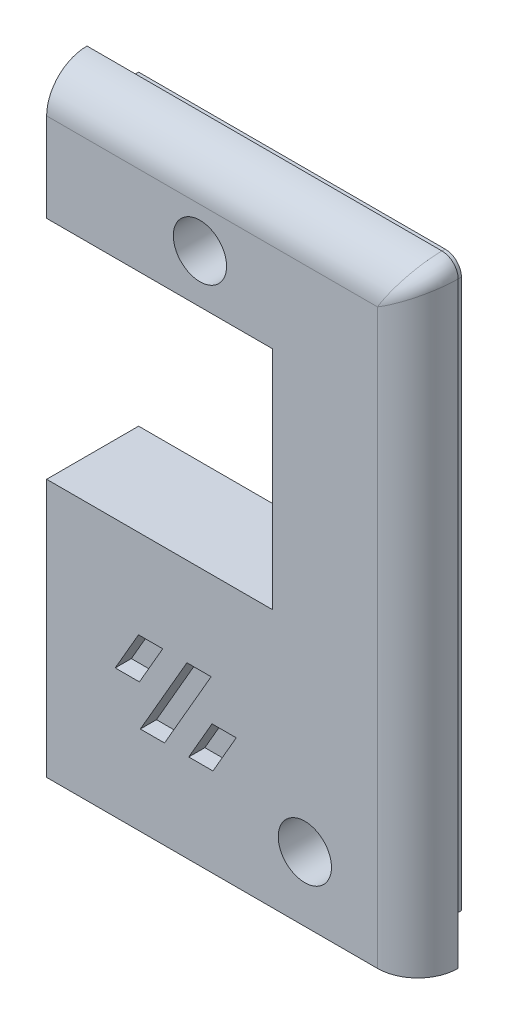
SolidWorks part; units mm, degrees
ref_plane "Front Plane" through (0, 0, 0) normal (0, 0, 1) x (1, 0, 0)
ref_plane "Top Plane" through (0, 0, 0) normal (0, 1, 0) x (1, 0, 0)
ref_plane "Right Plane" through (0, 0, 0) normal (1, 0, 0) x (0, 0, -1)
sketch "Sketch1" plane through (0, 0, 0) normal (0, 0, 1) x (1, 0, 0)
  line L1 (-14.899, 13.3838) -> (5.101, 13.3838)
  line L2 (-14.899, 13.3838) -> (-14.899, -21.6162)
  line L3 (-14.899, -21.6162) -> (5.101, -21.6162)
  line L4 (5.101, 13.3838) -> (5.101, -21.6162)
  dimension "D1" = 20
  dimension "D2" = 35
extrude "Boss-Extrude1" add sketch "Sketch1" along normal blind 3.2
fillet "Fillet1" radius 1 1 edges at (5.101, 13.3838, 1.6)
sketch "Sketch2" plane through (0, 0, 3.2) normal (0, 0, 1) x (1, 0, 0)
  line L0 (-14.899, 13.3838) -> (-14.899, -21.6162) construction
  line L1 (-14.899, -5.6162) -> (-0.899, -5.6162)
  line L2 (-14.899, -5.6162) -> (-14.899, 8.3838)
  line L3 (-14.899, 8.3838) -> (-0.899, 8.3838)
  line L4 (-0.899, -5.6162) -> (-0.899, 8.3838)
  line L5 (-14.899, -21.6162) -> (5.101, -21.6162) construction
  dimension "D1" = 16
  dimension "D2" = 14
  dimension "D3" = 14
extrude "Cut-Extrude1" cut sketch "Sketch2" against normal through all and the other way blind 12.5
sketch "Sketch4" plane through (0, 0, 3.2) normal (0, 0, 1) x (1, 0, 0)
  line L0 (4.101, 13.3838) -> (-14.899, 13.3838) construction
  line L1 (-14.899, 16.3838) -> (8.101, 16.3838)
  line L2 (-14.899, 16.3838) -> (-14.899, -21.6162)
  line L3 (-14.899, -21.6162) -> (8.101, -21.6162)
  line L4 (8.101, 16.3838) -> (8.101, -21.6162)
  line L5 (5.101, -21.6162) -> (5.101, 12.3838) construction
  dimension "D1" = 3
  dimension "D2" = 3
  dimension "D3" = 38
extrude "Boss-Extrude2" add sketch "Sketch4" along normal blind 2.5
fillet "Fillet2" radius 1 1 edges at (8.101, 16.3838, 4.45)
sketch "Sketch5" plane through (0, 0, 3.2) normal (0, 0, -1) x (-1, 0, 0)
  line L1 (0.899, 8.3838) -> (14.899, 8.3838)
  line L2 (0.899, 8.3838) -> (0.899, -5.6162)
  line L3 (0.899, -5.6162) -> (14.899, -5.6162)
  line L4 (14.899, 8.3838) -> (14.899, -5.6162)
extrude "Cut-Extrude2" cut sketch "Sketch5" against normal blind 2.5
fillet "Fillet3" radius 2.5 3 edges at (8.101, -3.1162, 5.7) (7.8081, 16.0909, 5.7) (-3.899, 16.3838, 5.7)
sketch "Sketch6" plane through (0, 0, 0) normal (0, 0, -1) x (-1, 0, 0)
  line L0 (14.899, -21.6162) -> (-5.101, -21.6162) construction
  line L1 (0.899, -5.6162) -> (0.899, 8.3838) construction
  circle A0 centre (-2.101, 5.3838) radius 1.4
  dimension "D1" = 2.8
  dimension "D2" = 27
  dimension "D3" = 3
sketch "Sketch12" plane through (0, 0, 5.7) normal (0, 0, 1) x (1, 0, 0)
  line L0 (-9.2056, -11.1162) -> (-7.7056, -11.1162)
  line L1 (-7.7056, -11.1162) -> (-9.149, -13.6162)
  line L2 (-9.149, -13.6162) -> (-10.649, -13.6162)
  line L3 (-10.649, -13.6162) -> (-9.2056, -11.1162)
  line L4 (-6.2056, -11.1162) -> (-4.7056, -11.1162)
  line L5 (-4.7056, -11.1162) -> (-7.5924, -16.1162)
  line L6 (-7.5924, -16.1162) -> (-9.0924, -16.1162)
  line L7 (-9.0924, -16.1162) -> (-6.2056, -11.1162)
  line L8 (-6.0924, -16.1162) -> (-4.5924, -16.1162)
  line L9 (-4.5924, -16.1162) -> (-3.149, -13.6162)
  line L10 (-3.149, -13.6162) -> (-4.649, -13.6162)
  line L11 (-4.649, -13.6162) -> (-6.0924, -16.1162)
  line L13 (-0.899, -5.6162) -> (-14.899, -5.6162) construction
  line L14 (-14.899, -5.6162) -> (-14.899, -21.6162) construction
  dimension "D1" = 1.5
  dimension "D2" = 1.5
  dimension "D3" = 1.5
  dimension "D4" = 1.5
  dimension "D5" = 1.5
  dimension "D6" = 1.5
  dimension "D7" = 5
  dimension "D10" = 1.5
  dimension "D11" = 1.5
  dimension "D12" = 8
  dimension "D13" = 4.25
extrude "Cut-Extrude5" cut sketch "Sketch12" against normal blind 1
extrude "Boss-Extrude3" add sketch "Sketch6" along normal blind 1.75
fillet "Fillet5" radius 1 1 edges at (0.701, 5.3838, -1.75)
sketch "Sketch13" plane through (0, 0, 5.7) normal (0, 0, 1) x (1, 0, 0)
  line L0 (5.101, -21.6162) -> (5.101, 12.3838) construction
  line L1 (-14.899, -21.6162) -> (5.101, -21.6162) construction
  circle A0 centre (1.101, -17.6162) radius 1.65
  point P4 (0, 0)
  point P6 (-7.5245, 14.6464)
  dimension "D1" = 3.3
  dimension "D2" = 4
  dimension "D3" = 4
extrude "Cut-Extrude6" cut sketch "Sketch13" against normal blind 10
sketch "Sketch14" plane through (0, 0, 0) normal (0, 0, -1) x (-1, 0, 0)
  line L1 (0.899, 8.3838) -> (14.899, 8.3838) construction
  line L3 (14.899, 13.3838) -> (14.899, 8.3838) construction
  circle A0 centre (5.399, 11.3838) radius 1.65
  dimension "D1" = 3.3
  dimension "D2" = 3
  dimension "D3" = 9.5
extrude "Cut-Extrude7" cut sketch "Sketch14" against normal blind 10
